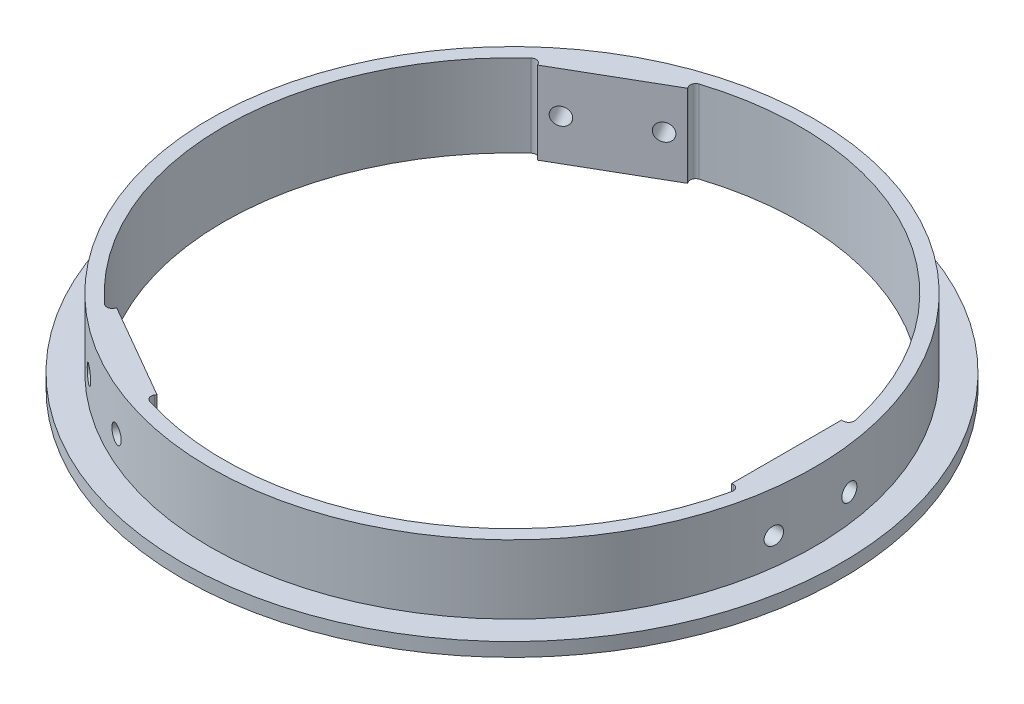
SolidWorks part; units mm, degrees
ref_plane "Front Plane" through (0, 0, 0) normal (0, 0, 1) x (1, 0, 0)
ref_plane "Top Plane" through (0, 0, 0) normal (0, 1, 0) x (1, 0, 0)
ref_plane "Right Plane" through (0, 0, 0) normal (1, 0, 0) x (0, 0, -1)
sketch "Sketch1" plane through (0, 0, 0) normal (0, 1, 0) x (1, 0, 0)
  circle A0 centre (0, 0) radius 152.4
  circle A1 centre (0, 0) radius 133.35
  dimension "D1" = 304.8
  dimension "D2" = 266.7
extrude "Boss-Extrude1" add sketch "Sketch1" along normal blind 38.1
sketch "Sketch2" plane through (0, 38.1, 0) normal (0, 1, 0) x (1, 0, 0)
  circle A0 centre (0, 0) radius 139.7
  circle A1 centre (0, 0) radius 152.4 construction
  circle A2 centre (0, 0) radius 152.4
  dimension "D1" = 279.4
extrude "Cut-Extrude1" cut sketch "Sketch2" against normal blind 31.75
sketch "Sketch3" plane through (0, 38.1, 0) normal (0, 1, 0) x (1, 0, 0)
  line L0 (127, 25.4) -> (127, -25.4)
  line L1 (127, 25.4) -> (130.9086, 25.4)
  line L2 (127, -25.4) -> (130.9086, -25.4)
  circle A0 centre (0, 0) radius 133.35 construction
  arc A1 (130.9086, -25.4) -> (130.9086, 25.4) centre (0, 0) ccw
  point P2 (127, 0)
  dimension "D1" = 50.8
  dimension "D2" = 127
extrude "Boss-Extrude2" add sketch "Sketch3" against normal through all
fillet "Fillet1" radius 2.54 2 edges at (130.9086, 19.05, -25.4) (130.9086, 19.05, 25.4)
hole_wizard "Hole1" positions "Sketch4" profile "Sketch5" legacy end condition through all
sketch "Sketch4" plane through (127, 0, -417.9439) normal (-1, 0, 0) x (0, 0, 1)
  line L6 (392.5439, 0) -> (443.3439, 0) construction
  line L7 (417.9439, 19.05) -> (417.9439, 0)
  line L8 (400.4814, 19.05) -> (435.4064, 19.05)
  line L10 (435.4064, 19.05) -> (443.3439, 19.05)
  line L11 (443.3439, 0) -> (443.3439, 38.1) construction
  point P0 (400.4814, 19.05)
  point P2 (435.4064, 19.05)
  point P40 (435.4064, 19.2808)
  dimension "D1" = 34.925
sketch "Sketch5" plane through (127, 19.05, -17.4625) normal (0, 1, 0) x (0, 0, 1)
  line L0 (0, 0) -> (0, 81.1823)
  line L1 (0, 81.1823) -> (4, 81.1823)
  line L2 (4, 81.1823) -> (4, 0)
  line L3 (4, 0) -> (0, 0)
  line L4 (0, 110) -> (0, -10) construction
  dimension "Diameter" = 8
  dimension "Depth" = 81.1823
pattern_circular "CirPattern1" count 3 over 360 about axis through (0, 38.1, 0) along (0, 1, 0) of "Boss-Extrude2", "Fillet1", "Hole1"
